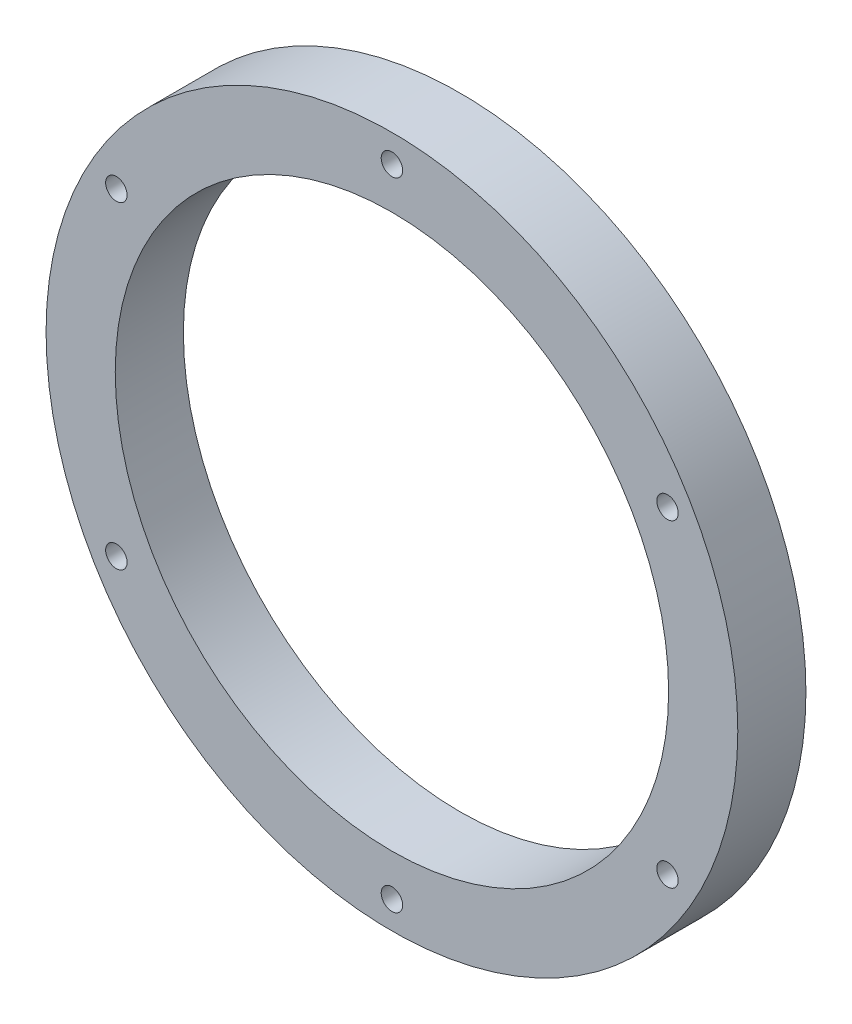
SolidWorks part; units mm, degrees
ref_plane "Ebene vorne" through (0, 0, 0) normal (0, 0, 1) x (1, 0, 0)
ref_plane "Ebene oben" through (0, 0, 0) normal (0, 1, 0) x (1, 0, 0)
ref_plane "Ebene rechts" through (0, 0, 0) normal (1, 0, 0) x (0, 0, -1)
sketch "Skizze1" plane through (0, 0, 0) normal (0, 0, 1) x (1, 0, 0)
  line L0 (0, 0) -> (-48526.5407, 0) construction
  line L2 (0, 0) -> (0, -48526.5407) construction
  circle A0 centre (0, 0) radius 40
  circle A1 centre (0, 0) radius 50
  dimension "D1" = 100
  dimension "D2" = 80
extrude "Aufsatz-Linear austragen1" add sketch "Skizze1" along normal blind 9.85
hole_wizard "Ø3.1 (3.1) Durchmesser Bohrung1" positions "Skizze2" profile "Skizze3" hole size "Ø3.1" standard "ISO" end condition through all
sketch "Skizze2" plane through (0, 0, 9.85) normal (0, 0, 1) x (1, 0, 0)
  line L0 (0, 0) -> (0, 50000) construction
  circle A0 centre (0, 0) radius 46 construction
  circle A1 centre (0, 0) radius 46 construction
  circle A2 centre (0, 0) radius 46 construction
  circle A3 centre (0, 0) radius 46 construction
  circle A4 centre (0, 0) radius 46 construction
  circle A5 centre (0, 0) radius 46 construction
  point P10 (0, 46)
  point P17 (39.8372, 23)
  point P19 (39.8372, -23)
  point P21 (0, -46)
  point P23 (-39.8372, -23)
  point P25 (-39.8372, 23)
  dimension "D1" = 92
  dimension "D2" = 6
sketch "Skizze3" plane through (-39.8372, 23, 9.85) normal (1, 0, 0) x (0, -1, 0)
  line L0 (0, 0) -> (0, 9.85)
  line L1 (0, 9.85) -> (1.55, 9.85)
  line L2 (1.55, 9.85) -> (1.55, 0)
  line L5 (1.55, 0) -> (0, 0)
  line L11 (0, -6.35) -> (0, 107.95) construction
  dimension "Bohrerdurchmesser" = 3.1
  dimension "Bohrungstiefe" = 9.85
